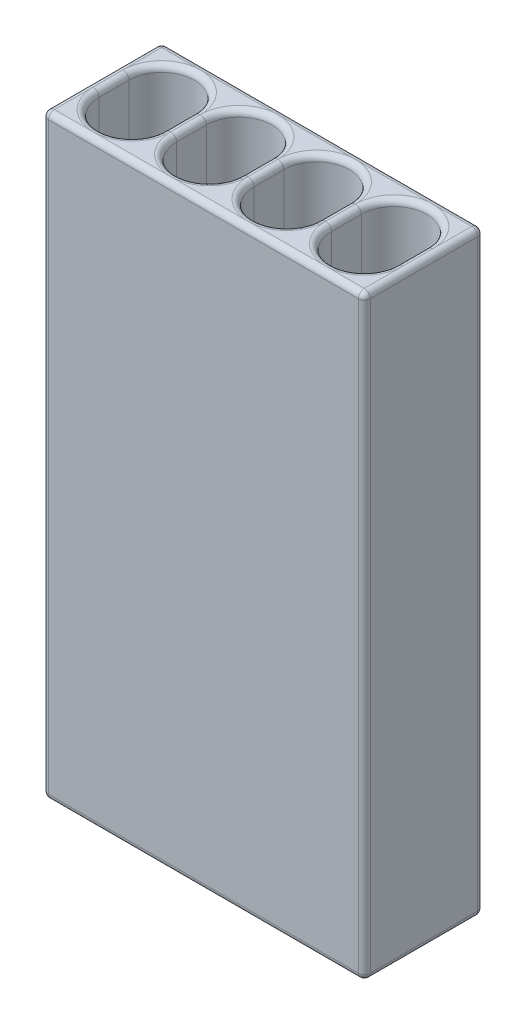
SolidWorks part; units mm, degrees
ref_plane "Front Plane" through (0, 0, 0) normal (0, 0, 1) x (1, 0, 0)
ref_plane "Top Plane" through (0, 0, 0) normal (0, 1, 0) x (1, 0, 0)
ref_plane "Right Plane" through (0, 0, 0) normal (1, 0, 0) x (0, 0, -1)
sketch "Sketch1" plane through (0, 0, 0) normal (0, 1, 0) x (1, 0, 0)
  line L0 (-15.4781, -1.9844) -> (-15.4781, 1.9844) construction
  line L1 (-19.8438, -1.9844) -> (-19.8438, 1.9844)
  line L2 (-11.1125, -1.9844) -> (-11.1125, 1.9844)
  line L3 (-5.1594, -1.9844) -> (-5.1594, 1.9844) construction
  line L4 (-9.525, -1.9844) -> (-9.525, 1.9844)
  line L5 (-0.7937, -1.9844) -> (-0.7938, 1.9844)
  line L6 (5.1594, -1.9844) -> (5.1594, 1.9844) construction
  line L7 (0.7937, -1.9844) -> (0.7937, 1.9844)
  line L8 (9.525, -1.9844) -> (9.525, 1.9844)
  line L9 (15.4781, -1.9844) -> (15.4781, 1.9844) construction
  line L10 (11.1125, -1.9844) -> (11.1125, 1.9844)
  line L11 (19.8438, -1.9844) -> (19.8437, 1.9844)
  line L12 (-0.7937, -1.9844) -> (0.7937, 1.9844) construction
  line L13 (15.4781, 6.35) -> (15.4781, 7.9375) construction
  line L14 (-21.4312, -7.9375) -> (21.4312, -7.9375)
  line L15 (-21.4312, -7.9375) -> (-21.4312, 7.9375)
  line L16 (-21.4312, 7.9375) -> (21.4312, 7.9375)
  line L17 (21.4312, -7.9375) -> (21.4312, 7.9375)
  line L18 (-21.4312, -7.9375) -> (21.4312, 7.9375) construction
  line L19 (-21.4312, 7.9375) -> (21.4312, -7.9375) construction
  line L20 (19.8437, 1.9844) -> (21.4312, 1.9844) construction
  arc A0 (-19.8438, -1.9844) -> (-11.1125, -1.9844) centre (-15.4781, -1.9844) ccw
  arc A1 (-11.1125, 1.9844) -> (-19.8438, 1.9844) centre (-15.4781, 1.9844) ccw
  arc A2 (-9.525, -1.9844) -> (-0.7937, -1.9844) centre (-5.1594, -1.9844) ccw
  arc A3 (-0.7938, 1.9844) -> (-9.525, 1.9844) centre (-5.1594, 1.9844) ccw
  arc A4 (0.7937, -1.9844) -> (9.525, -1.9844) centre (5.1594, -1.9844) ccw
  arc A5 (9.525, 1.9844) -> (0.7937, 1.9844) centre (5.1594, 1.9844) ccw
  arc A6 (11.1125, -1.9844) -> (19.8438, -1.9844) centre (15.4781, -1.9844) ccw
  arc A7 (19.8437, 1.9844) -> (11.1125, 1.9844) centre (15.4781, 1.9844) ccw
  point P3 (-15.4781, 0)
  point P8 (-15.4781, 6.35)
  point P9 (-15.4781, -6.35)
  point P13 (-5.1594, 0)
  point P20 (5.1594, 0)
  point P27 (15.4781, 0)
  point P33 (0, 0)
  point P42 (0, 0)
  dimension "D1" = 8.7312
  dimension "D2" = 12.7
  dimension "D4" = 1.5875
  dimension "D5" = 1.5875
  dimension "D3" = 4
extrude "Boss-Extrude1" add sketch "Sketch1" along normal blind 76.2
sketch "Sketch2" plane through (0, 0, 0) normal (0, -1, 0) x (1, 0, 0)
  line L4 (21.4312, -7.9375) -> (21.4312, 7.9375)
  line L5 (21.4312, 7.9375) -> (-21.4312, 7.9375)
  line L6 (-21.4312, 7.9375) -> (-21.4312, -7.9375)
  line L7 (-21.4312, -7.9375) -> (21.4312, -7.9375)
  line L8 (21.4312, -7.9375) -> (21.4312, 7.9375)
  line L9 (21.4312, 7.9375) -> (-21.4312, 7.9375)
  line L10 (-21.4312, 7.9375) -> (-21.4312, -7.9375)
  line L11 (-21.4312, -7.9375) -> (21.4312, -7.9375)
  dimension "D1" = 0
extrude "Boss-Extrude2" add sketch "Sketch2" along normal blind 3.175
sketch "Sketch3" plane through (0, 0, 0) normal (0, 1, 0) x (1, 0, 0)
  line L0 (19.8438, -1.9844) -> (11.1125, 1.9844) construction
  line L1 (-11.1125, -1.9844) -> (-19.8438, 1.9844) construction
  point P8 (15.4781, 0)
  point P9 (-15.4781, 0)
sketch "Sketch4" plane through (0, 0, 0) normal (0, 0, 1) x (1, 0, 0)
  line L0 (-15.4781, 0) -> (-19.5421, 0)
  line L1 (-11.1125, 0) -> (-19.8438, 0) construction
  line L2 (-19.5421, 0) -> (-17.3831, -2.4836)
  line L3 (-17.3831, -2.4836) -> (-17.3831, -3.175)
  line L4 (21.4312, -3.175) -> (-21.4312, -3.175) construction
  line L5 (-17.3831, -3.175) -> (-15.4781, -3.175)
  line L6 (-15.4781, -3.175) -> (-15.4781, 0) construction
  line L7 (-15.4781, 0) -> (-15.4781, -3.175)
  point P5 (-2.4003, -0.9702)
  point P11 (-1.2599, -3.2258)
  point P12 (-1.7252, -2.6905)
  point P13 (-15.4781, 0)
  dimension "D1" = 41
  dimension "D2" = 4.064
  dimension "D3" = 1.905
revolve "Cut-Revolve1" cut sketch "Sketch4" angle 360 about L6
mirror "Mirror1" about plane through (0, 0, 0) normal (1, 0, 0) of "Cut-Revolve1"
fillet "Fillet1" radius 0.7937 28 edges at (19.8438, 76.2, 0) (15.4781, 76.2, -6.35) (11.1125, 76.2, 0) (15.4781, 76.2, 6.35) (-0.7938, 76.2, 0) (-5.1594, 76.2, -6.35) (-9.525, 76.2, 0) (-5.1594, 76.2, 6.35) (0, 76.2, 7.9375) (-21.4312, 76.2, 0) (0, 76.2, -7.9375) (21.4312, 76.2, 0) (-11.1125, 76.2, 0) (-15.4781, 76.2, -6.35) (-19.8438, 76.2, 0) (-15.4781, 76.2, 6.35) (9.525, 76.2, 0) (5.1594, 76.2, -6.35) (0.7937, 76.2, 0) (5.1594, 76.2, 6.35) (21.4312, 36.5125, -7.9375) (21.4312, 36.5125, 7.9375) (-21.4312, 36.5125, -7.9375) (-21.4312, 36.5125, 7.9375) (21.4312, -3.175, 0) (0, -3.175, -7.9375) (-21.4312, -3.175, 0) (0, -3.175, 7.9375)
